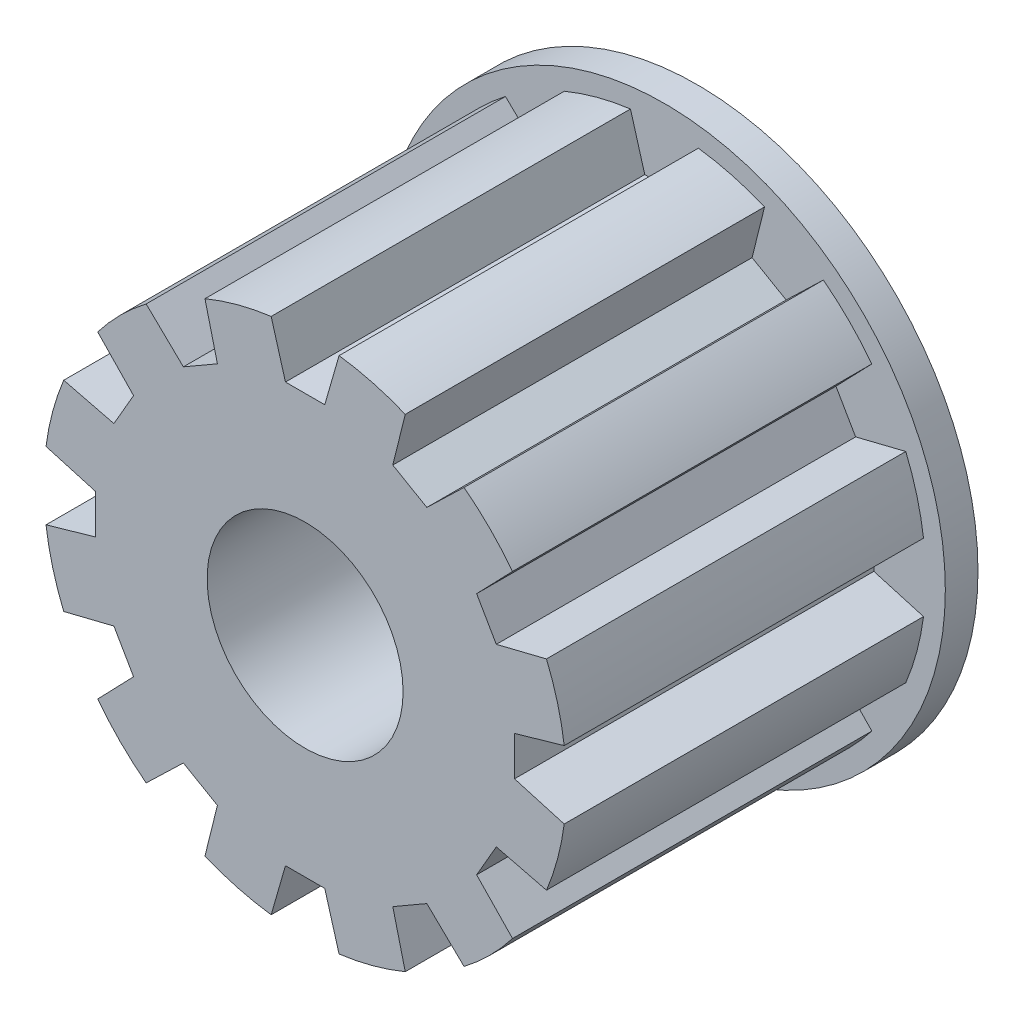
SolidWorks part; units mm, degrees
ref_plane "Front Plane" through (0, 0, 0) normal (0, 0, 1) x (1, 0, 0)
ref_plane "Top Plane" through (0, 0, 0) normal (0, 1, 0) x (1, 0, 0)
ref_plane "Right Plane" through (0, 0, 0) normal (1, 0, 0) x (0, 0, -1)
sketch "Sketch1" plane through (0, 0, 0) normal (0, 0, 1) x (1, 0, 0)
  circle A0 centre (0, 0) radius 4
  circle A1 centre (0, 0) radius 1.5
extrude "Boss-Extrude1" add sketch "Sketch1" along normal blind 6
sketch "Sketch2" plane through (0, 0, 0) normal (0, 0, 1) x (1, 0, 0)
  line L0 (3.2056, -0.3009) -> (4.3545, -0.6314)
  line L1 (4.3545, -0.6314) -> (4.3545, 0.6314)
  line L2 (4.3545, 0.6314) -> (3.2056, 0.3009)
  line L3 (3.2056, 0.3009) -> (3.2056, -0.3009)
extrude "Cut-Extrude2" cut sketch "Sketch2" along normal blind 6.2
ref_axis "Axis1" through (0, 0, -0.3) along (0, 0, 1)
pattern_circular "CirPattern1" count 12 every 30 about axis through (0, 0, -0.3) along (0, 0, 1) of "Cut-Extrude2"
sketch "Sketch3" plane through (0, 0, 0) normal (0, 0, 1) x (1, 0, 0)
  circle A0 centre (0, 0) radius 4.3
  circle A1 centre (0, 0) radius 1.5
extrude "Boss-Extrude2" add sketch "Sketch3" along normal blind 0.5
